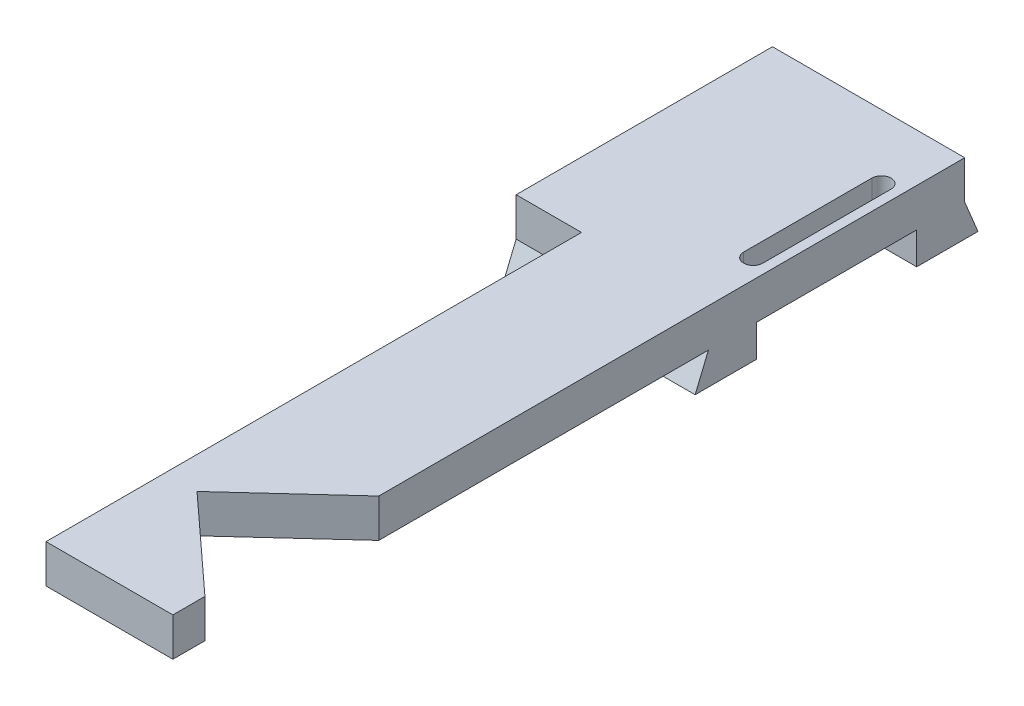
SolidWorks part; units mm, degrees
ref_plane "Front Plane" through (0, 0, 0) normal (0, 0, 1) x (1, 0, 0)
ref_plane "Top Plane" through (0, 0, 0) normal (0, 1, 0) x (1, 0, 0)
ref_plane "Right Plane" through (0, 0, 0) normal (1, 0, 0) x (0, 0, -1)
sketch "Sketch1" plane through (0, 0, 0) normal (0, 1, 0) x (1, 0, 0)
  line L0 (0, 8.1676) -> (-6.8534, 0)
  line L1 (-6.8534, 0) -> (0, -8.1676)
  line L2 (0, -8.1676) -> (0, -20)
  line L5 (0, 20) -> (0, 8.1676)
  line L6 (0, 0) -> (25.3033, 0) construction
  line L8 (-30, 20) -> (-30, -20)
  line L11 (-30, 20) -> (0, 20)
  line L12 (-30, -20) -> (0, -20)
  line L13 (0, -8.1676) -> (0, 8.1676)
  circle A0 centre (0, 0) radius 5.25 construction
  circle A1 centre (0, 0) radius 20 construction
  dimension "D2" = 10.5
  dimension "D7" = 40
  dimension "D1" = 100
  dimension "D4" = 30
extrude "Boss-Extrude1" add sketch "Sketch1" along normal blind 6 contours L8 L12 L2 L1 L0 L5 L11 | L1 L13 L0 region at (-2.2845, 0, 0) region at (-15.6222, 0, 0)
sketch "Sketch7" plane through (-30, 0, 0) normal (1, 0, 0) x (0, 0, -1)
  line L0 (20, -8.8983) -> (20, 12.3176) construction
  line L1 (-20, 13.2103) -> (-20, -9.9633) construction
  line L2 (0, 0) -> (0, -10.31) construction
  line L3 (-20, 0) -> (-21.8199, -5) construction
  line L4 (-21.8199, -5) -> (-12.5, -5)
  line L5 (-12.5, -5) -> (-12.5, 0)
  line L6 (-21.8199, -5) -> (-22.0699, -5)
  line L7 (-12.5, 0) -> (-20, 0)
  line L8 (12.5, 0) -> (20, 0)
  line L9 (12.5, -5) -> (12.5, 0)
  line L10 (21.8199, -5) -> (12.5, -5)
  line L11 (20, 0) -> (21.8199, -5) construction
  line L12 (20, 0) -> (-20, 0) construction
  line L13 (-22.0699, -5) -> (-20, 0)
  line L14 (22.0699, -5) -> (20, 0)
  line L15 (21.8199, -5) -> (22.0699, -5)
  point P15 (0, 0)
  dimension "D1" = 40
  dimension "D4" = 5
  dimension "D5" = 70
  dimension "D2" = 7.5
  dimension "D3" = 0.25
extrude "Dove Boss" add sketch "Sketch7" along normal up to surface (30 mm away) contours L5 L4 L3 region at (-30, -2.601, 16.7884) up to face at (0, 3, 0)
extrude "Boss-Extrude7" add sketch "Sketch7<3>" along normal up to surface (30 mm away) contours L11 L10 L9 region at (-30, -2.601, -16.7884) up to face at (0, 0.2857, 6.7243)
sketch "Sketch7<3>" plane through (-30, 0, 0) normal (1, 0, 0) x (0, 0, -1) same geometry as "Sketch7"
sketch "Sketch4" plane through (0, 0, 0) normal (0, 1, 0) x (1, 0, 0)
  line L0 (-3, 10) -> (-3, -10) construction
  line L1 (-1.5, 10) -> (-1.5, -10)
  line L2 (-4.5, 10) -> (-4.5, -10)
  arc A0 (-1.5, 10) -> (-4.5, 10) centre (-3, 10) ccw
  arc A1 (-4.5, -10) -> (-1.5, -10) centre (-3, -10) ccw
  point P2 (-3, 0)
  dimension "D1" = 3
  dimension "D2" = 3
  dimension "D4" = 20
extrude "Pin Slot" cut sketch "Sketch4" along normal up to next and the other way through all
sketch "Sketch8" plane through (0, 6, 0) normal (0, 1, 0) x (1, 0, 0)
  line L0 (0, -98.5634) -> (-14.8019, -85)
  line L1 (-19.8019, -20) -> (0, -20)
  line L2 (-19.8019, -20) -> (-19.8019, -103.5634)
  line L3 (-19.8019, -103.5634) -> (0, -103.5634)
  line L4 (0, -20) -> (0, -71.4366)
  line L5 (-14.8019, -85) -> (0, -71.4366)
  line L6 (0, -98.5634) -> (0, -103.5634)
  line L7 (20.6764, -85) -> (-23.1655, -85) construction
  line L8 (0, -98.5634) -> (0, -71.4366) construction
  line L10 (0, 20) -> (0, -20) construction
  circle A0 centre (0, -85) radius 10 construction
  point P16 (0, 0)
  line M34 (-30, -20) -> (0, -20)
  dimension "D3" = 20
  dimension "D1" = 85
  dimension "D2" = 5
  dimension "D4" = 85
  dimension "D5" = 5
extrude "Boss-Extrude8" add sketch "Sketch8" against normal up to surface (6 mm away) contours L4 L2 L3 L6 L0 L5 M34 region at (-10.5868, 6, 58.5757) up to face at (-3, 0, 0)
equation "\"doveAngle\"=70"
equation "\"D5@Sketch7\"=\"doveAngle\""
